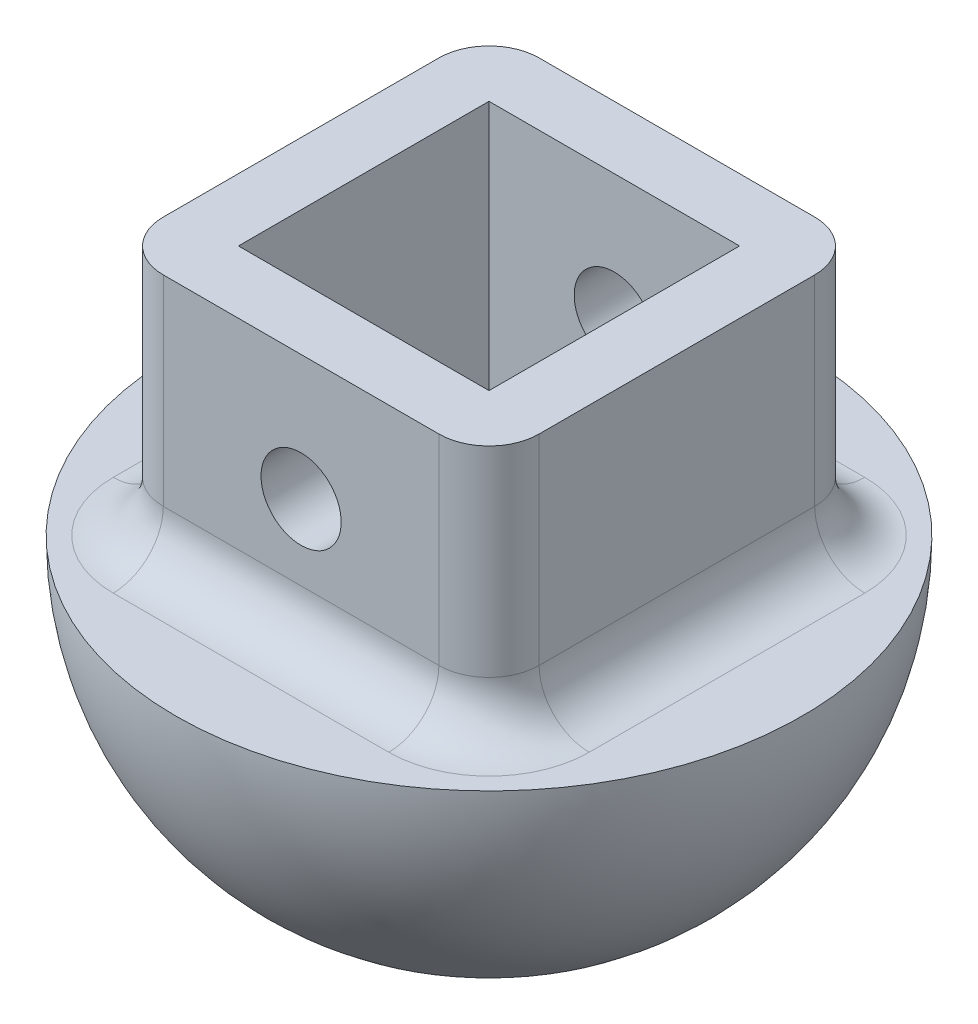
SolidWorks part; units mm, degrees
ref_plane "Front Plane" through (0, 0, 0) normal (0, 0, 1) x (1, 0, 0)
ref_plane "Top Plane" through (0, 0, 0) normal (0, 1, 0) x (1, 0, 0)
ref_plane "Right Plane" through (0, 0, 0) normal (1, 0, 0) x (0, 0, -1)
sketch "Sketch4" plane through (0, 0, 0) normal (0, 1, 0) x (1, 0, 0)
  line L0 (-12.5, 0) -> (12.5, 0)
  arc A0 (-12.5, 0) -> (12.5, 0) centre (0, 0) ccw
  point P8 (0, 0)
  dimension "D1" = 25
revolve "Revolve2" add sketch "Sketch4" angle 180 about L0 region at (0, 0, 5.3052)
sketch "Sketch1" plane through (0, 0, 0) normal (0, 1, 0) x (1, 0, 0)
  line L1 (-5, 5) -> (5, 5)
  line L2 (-5, 5) -> (-5, -5)
  line L3 (-5, -5) -> (5, -5)
  line L4 (5, 5) -> (5, -5)
  line L5 (-5, 5) -> (5, -5) construction
  line L6 (-5, -5) -> (5, 5) construction
  line L7 (-7.5, 7.5) -> (7.5, 7.5)
  line L8 (-7.5, 7.5) -> (-7.5, -7.5)
  line L9 (-7.5, -7.5) -> (7.5, -7.5)
  line L10 (7.5, 7.5) -> (7.5, -7.5)
  line L11 (-7.5, 7.5) -> (7.5, -7.5) construction
  line L12 (-7.5, -7.5) -> (7.5, 7.5) construction
  point P0 (0, 0)
  point P6 (0, 0)
  dimension "D1" = 10
  dimension "D2" = 15
extrude "Boss-Extrude1" add sketch "Sketch1" along normal blind 10
sketch "Sketch2" plane through (0, 0, 5) normal (0, 0, -1) x (-1, 0, 0)
  line L0 (0, 0) -> (0, 10) construction
  line L1 (-7.5, 10) -> (7.5, 10) construction
  circle A0 centre (0, 5) radius 1.6
  dimension "D1" = 3.2
extrude "Cut-Extrude1" cut sketch "Sketch2" against normal blind 10 and the other way blind 20
fillet "Fillet1" radius 2 8 edges at (-7.5, 5, 7.5) (-7.5, 5, -7.5) (7.5, 5, -7.5) (7.5, 5, 7.5) (0, 0, -7.5) (7.5, 0, 0) (-7.5, 0, 0) (0, 0, 7.5)
